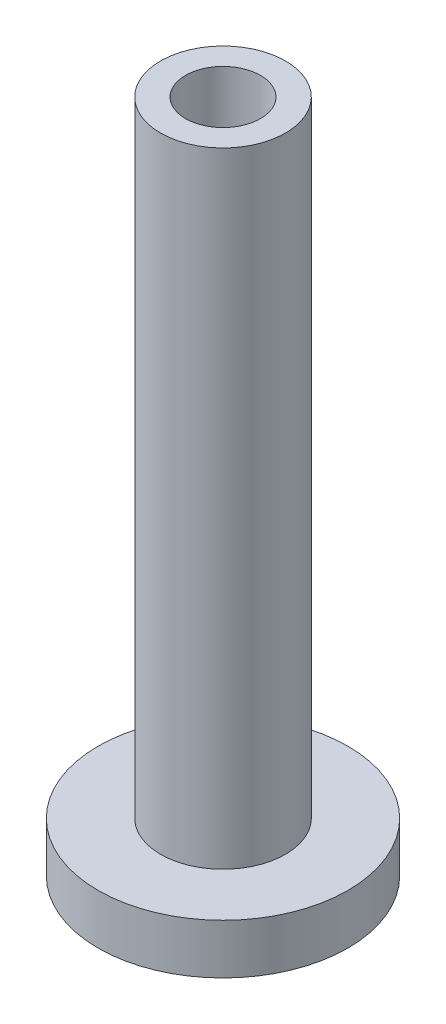
SolidWorks part; units mm, degrees
material "AISI 316 Annealed Stainless Steel Bar (SS)"
ref_plane "Front Plane" through (0, 0, 0) normal (0, 0, 1) x (1, 0, 0)
ref_plane "Top Plane" through (0, 0, 0) normal (0, 1, 0) x (1, 0, 0)
ref_plane "Right Plane" through (0, 0, 0) normal (1, 0, 0) x (0, 0, -1)
sketch "Sketch2" plane through (0, 0, 0) normal (0, 1, 0) x (1, 0, 0)
  circle A0 centre (0, 0) radius 2.5
  circle A1 centre (0, 0) radius 5
  dimension "D1" = 5
  dimension "D2" = 10
extrude "Boss-Extrude1" add sketch "Sketch2" against normal blind 2 contours A1 A0 | A0 region at (0, 0, 0) region at (-4.8586, 0, 0)
extrude "Boss-Extrude2" add sketch "Sketch2<3>" along normal blind 25 contours A0 region at (0, 0, 0)
sketch "Sketch2<3>" plane through (0, 0, 0) normal (0, 1, 0) x (1, 0, 0) same geometry as "Sketch2"
sketch "Sketch3" plane through (0, 25, 0) normal (0, 1, 0) x (1, 0, 0)
  circle A0 centre (0, 0) radius 1.5
  circle A1 centre (0, 0) radius 2.5 construction
  dimension "D1" = 1
extrude "Cut-Extrude1" cut sketch "Sketch3" along normal through all from surface starting at face at (0, 0, 2.5)
